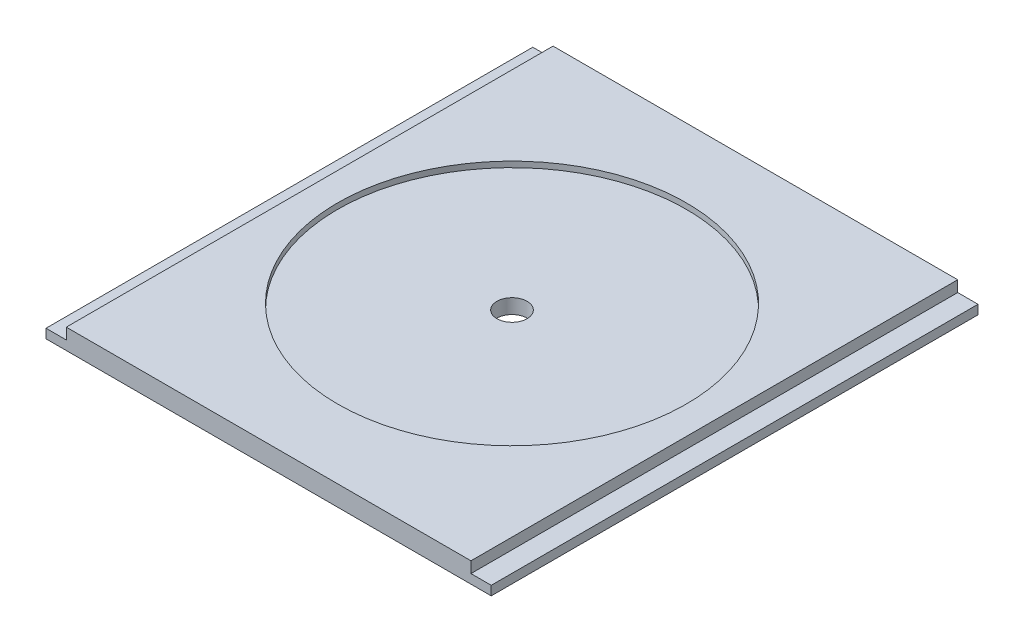
SolidWorks part; units mm, degrees
ref_plane "Front Plane" through (0, 0, 0) normal (0, 0, 1) x (1, 0, 0)
ref_plane "Top Plane" through (0, 0, 0) normal (0, 1, 0) x (1, 0, 0)
ref_plane "Right Plane" through (0, 0, 0) normal (1, 0, 0) x (0, 0, -1)
sketch "Sketch1" plane through (0, 0, 0) normal (0, 1, 0) x (1, 0, 0)
  line L1 (0, 0) -> (139.4003, 0)
  line L2 (0, 0) -> (0, 152.4)
  line L3 (0, 152.4) -> (139.4003, 152.4)
  line L4 (139.4003, 0) -> (139.4003, 152.4)
  dimension "D1" = 152.4
  dimension "D2" = 139.4003
extrude "Boss-Extrude1" add sketch "Sketch1" along normal blind 6.35
sketch "Sketch2" plane through (0, 6.35, 0) normal (0, 1, 0) x (1, 0, 0)
  line L0 (0, 0) -> (139.4003, 0) construction
  line L1 (0, 152.4) -> (6.35, 152.4)
  line L2 (0, 152.4) -> (0, 0)
  line L3 (0, 0) -> (6.35, 0)
  line L4 (6.35, 152.4) -> (6.35, 0)
  line L6 (139.4003, 152.4) -> (133.0503, 152.4)
  line L7 (139.4003, 152.4) -> (139.4003, 0)
  line L8 (139.4003, 0) -> (133.0503, 0)
  line L9 (133.0503, 152.4) -> (133.0503, 0)
  dimension "D1" = 6.35
  dimension "D2" = 6.35
extrude "Cut-Extrude1" cut sketch "Sketch2" against normal blind 3.4747
sketch "Sketch3" plane through (0, 6.35, 0) normal (0, 1, 0) x (1, 0, 0)
  line L0 (6.35, 0) -> (133.0503, 0) construction
  circle A0 centre (69.7001, 76.2) radius 54.5821
  point P2 (0, 0)
  point P5 (69.7001, 0)
  dimension "D1" = 109.1641
  dimension "D2" = 76.2
extrude "Cut-Extrude2" cut sketch "Sketch3" against normal blind 1.778
sketch "Sketch4" plane through (0, 4.572, 0) normal (0, 1, 0) x (1, 0, 0)
  circle A0 centre (69.7001, 76.2) radius 4.7219
  dimension "D1" = 9.4437
extrude "Cut-Extrude3" cut sketch "Sketch4" against normal through all
